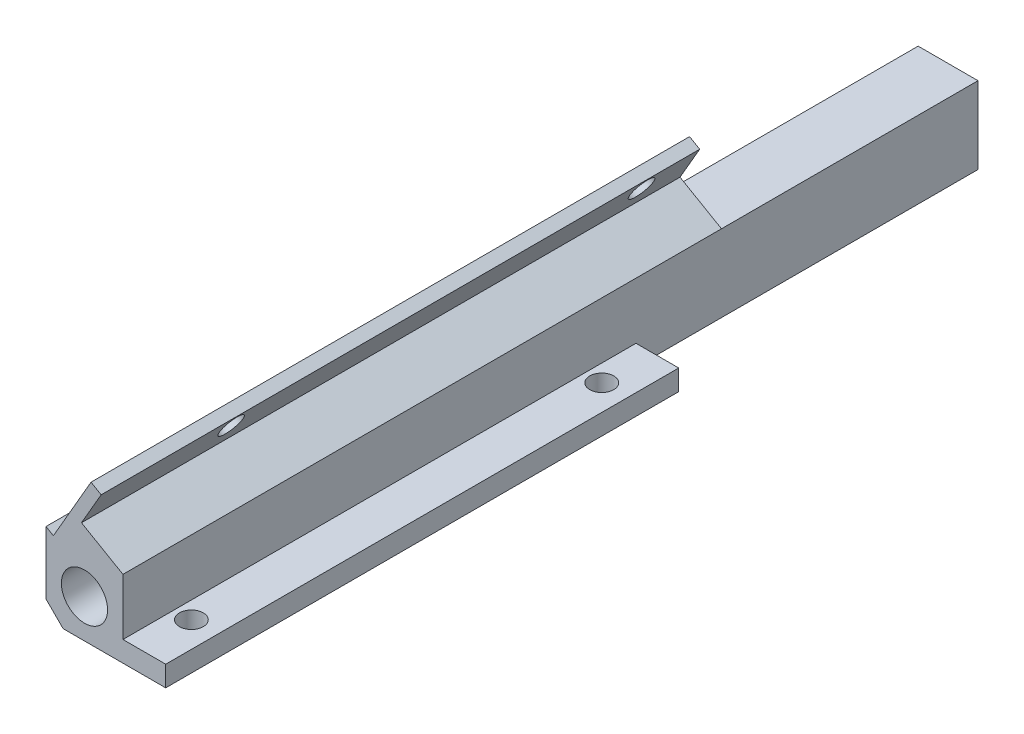
SolidWorks part; units mm, degrees
ref_plane "Front Plane" through (0, 0, 0) normal (0, 0, 1) x (1, 0, 0)
ref_plane "Top Plane" through (0, 0, 0) normal (0, 1, 0) x (1, 0, 0)
ref_plane "Right Plane" through (0, 0, 0) normal (1, 0, 0) x (0, 0, -1)
sketch "Sketch1" plane through (0, 0, 0) normal (0, 1, 0) x (1, 0, 0)
  line L1 (0, 0) -> (77.47, 0)
  line L2 (0, 0) -> (0, 127)
  line L3 (0, 127) -> (77.47, 127)
  line L4 (77.47, 0) -> (77.47, 127)
  dimension "D1" = 77.47
  dimension "D2" = 127
extrude "Boss-Extrude1" add sketch "Sketch1" along normal blind 11.43
sketch "Sketch2" plane through (0, 0, 0) normal (0, 0, 1) x (1, 0, 0)
  line L0 (5.715, 5.715) -> (71.755, 5.715) construction
  line L1 (38.735, 11.43) -> (38.735, 0) construction
  line L2 (0, 11.43) -> (77.47, 11.43) construction
  line L3 (0, 0) -> (77.47, 0) construction
  circle A0 centre (5.715, 5.715) radius 3.429
  circle A1 centre (71.755, 5.715) radius 3.429
  point P10 (38.735, 5.715)
  dimension "D1" = 6.858
  dimension "D2" = 66.04
extrude "Cut-Extrude1" cut sketch "Sketch2" against normal through all
sketch "Sketch3" plane through (0, 11.43, 0) normal (0, 1, 0) x (1, 0, 0)
  line L0 (11.43, 127) -> (11.43, 88.9)
  line L1 (77.47, 127) -> (0, 127) construction
  line L2 (11.43, 127) -> (66.04, 127)
  line L3 (66.04, 127) -> (66.04, 88.9)
  line L4 (53.34, 76.2) -> (24.13, 76.2)
  line L5 (0, 127) -> (0, 0) construction
  arc A0 (66.04, 88.9) -> (53.34, 76.2) centre (53.34, 88.9) cw
  arc A1 (24.13, 76.2) -> (11.43, 88.9) centre (24.13, 88.9) cw
  point P10 (38.735, 127)
  dimension "D1" = 12.7
  dimension "D2" = 11.43
  dimension "D3" = 50.8
extrude "Cut-Extrude2" cut sketch "Sketch3" against normal through all
sketch "Sketch4" plane through (0, 0, -127) normal (0, 0, -1) x (-1, 0, 0)
  line L0 (-11.43, 0) -> (-11.43, 11.43) construction
  line L1 (-66.04, 11.43) -> (-11.43, 11.43)
  line L2 (-66.04, 11.43) -> (-66.04, 5.08)
  line L3 (-66.04, 5.08) -> (-11.43, 5.08)
  line L4 (-11.43, 11.43) -> (-11.43, 5.08)
  line L5 (-11.43, 0) -> (0, 0) construction
  dimension "D1" = 5.08
extrude "Cut-Extrude3" cut sketch "Sketch4" against normal through all
chamfer "Chamfer1" distance 2.54 angle 45 4 edges at (0, 0, -63.5) (0, 11.43, -63.5) (77.47, 0, -63.5) (77.47, 11.43, -63.5)
sketch "Sketch5" plane through (0, 11.43, 0) normal (0, 1, 0) x (1, 0, 0)
  line L0 (11.43, 88.9) -> (11.43, 76.2)
  line L1 (11.43, 0) -> (11.43, 88.9) construction
  line L2 (11.43, 76.2) -> (77.47, 76.2)
  line L3 (77.47, 127) -> (77.47, 0) construction
  line L4 (77.47, 76.2) -> (77.47, 127)
  line L8 (24.13, 76.2) -> (53.34, 76.2) construction
  line L9 (77.47, 127) -> (11.43, 127)
  line L10 (11.43, 127) -> (11.43, 88.9)
extrude "Cut-Extrude4" cut sketch "Sketch5" against normal through all
sketch "Sketch6" plane through (0, 11.43, 0) normal (0, 1, 0) x (1, 0, 0)
  line L0 (24.13, 76.2) -> (24.13, 0)
  line L1 (11.43, 76.2) -> (66.04, 76.2) construction
  line L2 (66.04, 0) -> (11.43, 0) construction
  line L3 (24.13, 0) -> (77.47, 0)
  line L4 (77.47, 0) -> (77.47, 76.2)
  line L5 (77.47, 76.2) -> (24.13, 76.2)
  line L6 (11.43, 0) -> (11.43, 76.2) construction
  dimension "D1" = 12.7
extrude "Cut-Extrude5" cut sketch "Sketch6" against normal through all
sketch "Sketch7" plane through (0, 5.08, 0) normal (0, 1, 0) x (1, 0, 0)
  line L0 (11.43, 76.2) -> (24.13, 76.2) construction
  line L1 (11.43, 0) -> (11.43, 76.2) construction
  circle A0 centre (13.97, 68.58) radius 1.778
  circle A1 centre (13.97, 7.62) radius 1.778
  dimension "D1" = 3.556
  dimension "D2" = 7.62
  dimension "D3" = 68.58
  dimension "D4" = 2.54
extrude "Hole Cuts 1" cut sketch "Sketch7" against normal through all
sketch "Sketch17" plane through (0, 0, 0) normal (0, 0, 1) x (1, 0, 0)
  line L0 (0, 8.89) -> (0, 11.8699)
  line L1 (0, 11.8699) -> (5.588, 21.5486)
  line L2 (5.588, 21.5486) -> (8.8517, 19.6643)
  line L3 (8.8517, 19.6643) -> (5.9307, 14.605)
  line L4 (5.9307, 14.605) -> (11.43, 11.43)
  line L5 (0, 8.89) -> (0, 2.54) construction
  line L6 (11.43, 11.43) -> (2.54, 11.43)
  line L7 (2.54, 11.43) -> (0, 8.89)
  dimension "D1" = 11.176
  dimension "D2" = 5.842
  dimension "D3" = 6.35
  dimension "D4" = 60
extrude "Boss-Extrude5" add sketch "Sketch17" against normal blind 88.9
sketch "Sketch18" plane through (0, 0, 0) normal (0, 0, 1) x (1, 0, 0)
  line L0 (2.54, 0) -> (17.78, 0) construction
  line L1 (2.54, 0) -> (24.13, 0) construction
  line L2 (11.43, 5.08) -> (11.43, 11.43) construction
  line L3 (17.78, 0) -> (24.13, 0)
  line L4 (24.13, 0) -> (24.13, 5.08)
  line L5 (24.13, 5.08) -> (17.78, 5.08)
  line L6 (24.13, 5.08) -> (11.43, 5.08) construction
  line L7 (17.78, 5.08) -> (17.78, 0)
  dimension "D1" = 6.35
extrude "Cut-Extrude13" cut sketch "Sketch18" against normal blind 76.2
sketch "Sketch19" plane through (-1.8761, 1.0832, 0) normal (0.866, -0.5, 0) x (0, 0, -1)
  line L1 (88.9, 15.6137) -> (0, 15.6137) construction
  line L2 (88.9, 15.6137) -> (88.9, 21.4557) construction
  circle A0 centre (20.32, 19.4237) radius 1.778
  circle A1 centre (81.28, 19.4237) radius 1.778
  dimension "D1" = 3.556
  dimension "D2" = 7.62
  dimension "D3" = 68.58
  dimension "D4" = 3.81
extrude "Hole Cuts 2" cut sketch "Sketch19" against normal up to next
sketch "Sketch20" plane through (-5.1398, 2.9675, 0) normal (-0.866, 0.5, 0) x (0, 0, 1)
  line L1 (-88.9, 21.4557) -> (0, 21.4557)
  line L2 (-88.9, 21.4557) -> (-88.9, 10.2797)
  line L3 (-88.9, 10.2797) -> (0, 10.2797)
  line L4 (0, 21.4557) -> (0, 10.2797)
extrude "Cut-Extrude16" cut sketch "Sketch20" against normal blind 1.27
sketch "Sketch21" plane through (-1.8761, 1.0832, 0) normal (0.866, -0.5, 0) x (0, 0, -1)
  line L1 (88.9, 21.4557) -> (0, 21.4557)
  line L2 (88.9, 21.4557) -> (88.9, 15.6137)
  line L3 (88.9, 15.6137) -> (0, 15.6137)
  line L4 (0, 21.4557) -> (0, 15.6137)
extrude "Cut-Extrude17" cut sketch "Sketch21" against normal blind 0.762
sketch "Sketch22" plane through (0, 5.08, 0) normal (0, 1, 0) x (1, 0, 0)
  line L1 (17.78, 0) -> (11.43, 0)
  line L2 (17.78, 0) -> (17.78, 76.2)
  line L3 (17.78, 76.2) -> (11.43, 76.2)
  line L4 (11.43, 0) -> (11.43, 76.2)
extrude "Cut-Extrude18" cut sketch "Sketch22" against normal blind 2.032
